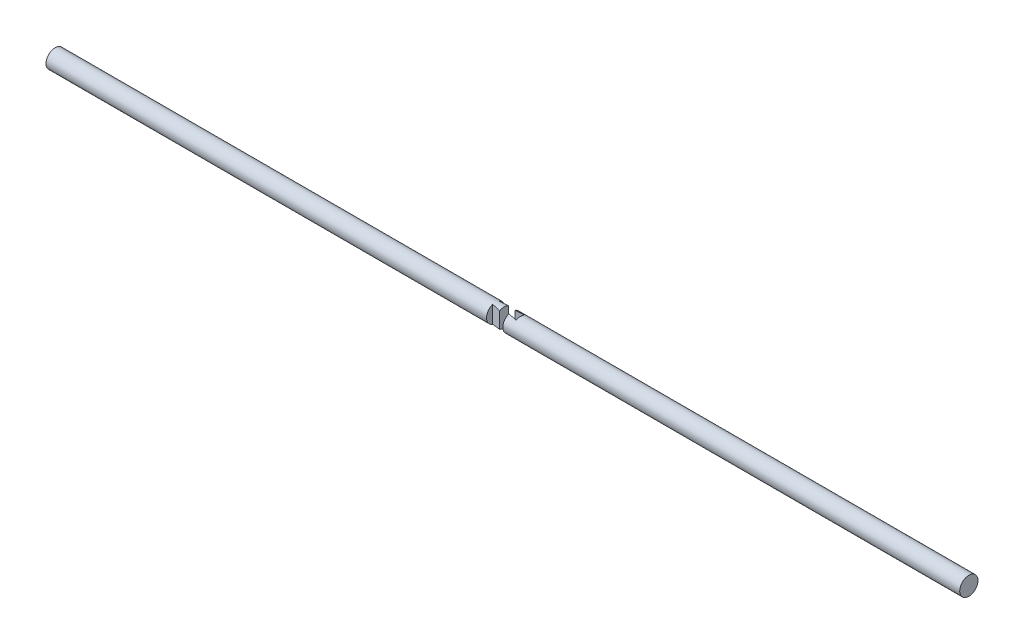
SolidWorks part; units mm, degrees
ref_plane "Front Plane" through (0, 0, 0) normal (0, 0, 1) x (1, 0, 0)
ref_plane "Top Plane" through (0, 0, 0) normal (0, 1, 0) x (1, 0, 0)
ref_plane "Right Plane" through (0, 0, 0) normal (1, 0, 0) x (0, 0, -1)
sketch "Sketch1" plane through (0, 0, 0) normal (1, 0, 0) x (0, 0, -1)
  circle A0 centre (0, 0) radius 4
  dimension "D1" = 8
extrude "Boss-Extrude1" add sketch "Sketch1" along normal blind 400
sketch "Sketch2" plane through (0, 0, 0) normal (0, 1, 0) x (1, 0, 0)
  line L0 (199.9857, 1.3) -> (200, 4)
  line L1 (199.9857, 1.3) -> (203.7287, 1.96)
  line L2 (203.7287, 1.96) -> (203.7287, -1.96)
  line L3 (203.7287, -1.96) -> (199.9857, -1.3)
  line L4 (199.9857, -1.3) -> (200, -4)
  line L5 (0, -4) -> (400, -4) construction
  line L6 (400, 4) -> (0, 4) construction
  line L7 (203.7287, 1.96) -> (203.7287, 4) construction
  line L8 (203.7287, -1.96) -> (203.7287, -4) construction
  line L9 (199.9857, 1.3) -> (202.1778, 1.3) construction
  line L10 (199.9857, -1.3) -> (202.5511, -1.3) construction
  line L11 (192.8374, 1.3) -> (192.8516, 4)
  line L12 (192.8374, 1.3) -> (196.5803, 1.96)
  line L13 (196.5803, 1.96) -> (196.5803, -1.96)
  line L14 (192.8374, -1.3) -> (192.8517, -4)
  line L15 (196.5803, -1.96) -> (192.8374, -1.3)
  line L16 (192.8516, 4) -> (200, 4)
  line L17 (192.8517, -4) -> (200, -4)
  line L18 (191.0267, 4) -> (191.0267, -4) construction
  line L19 (191.0267, 0) -> (205.857, 0) construction
  line L20 (203.7287, 1.96) -> (199.6033, 0) construction
  line L21 (199.6033, 0) -> (203.7287, -1.96) construction
  point P24 (196.5803, 0)
  point P27 (203.7287, 0)
  dimension "D1" = 10
  dimension "D2" = 10
  dimension "D3" = 2.7
extrude "Cut-Extrude3" cut sketch "Sketch2" against normal through all both and the other way through all
equation "\"Axle_length\"= 300mm"
equation "\"axle_diametet\"=5"
